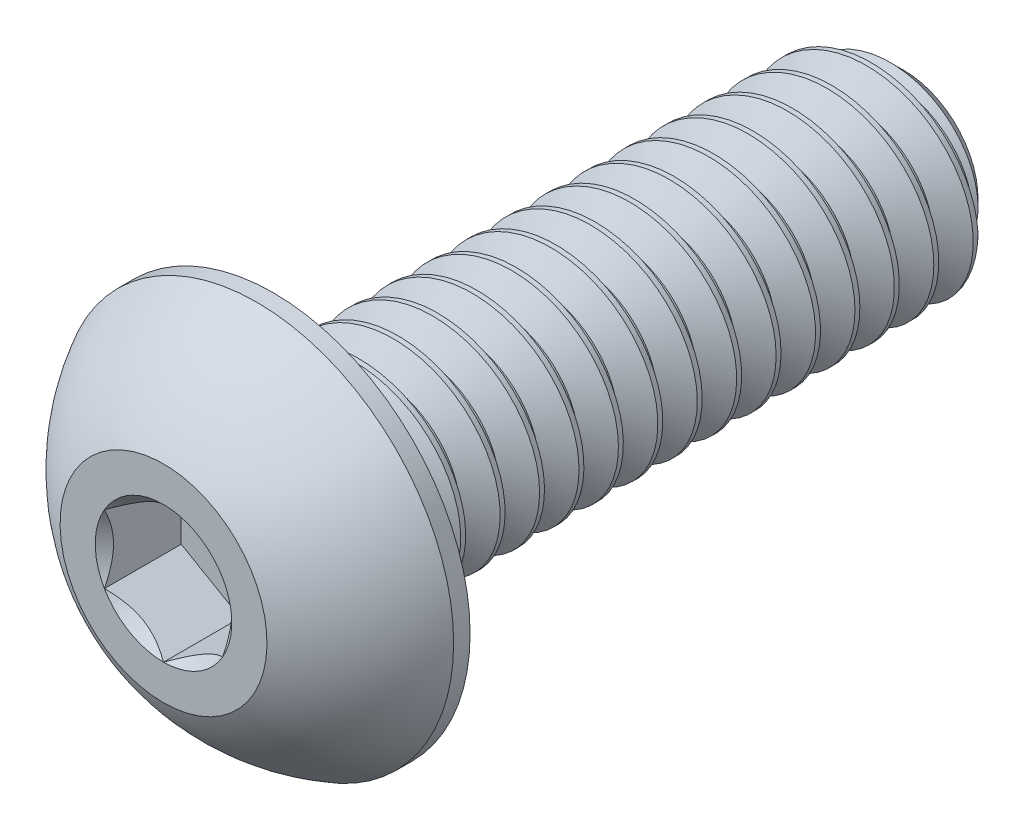
SolidWorks part; units mm, degrees
material "AISI 304"
ref_plane "Front" through (0, 0, 0) normal (0, 0, 1) x (1, 0, 0)
ref_plane "Top" through (0, 0, 0) normal (0, 1, 0) x (1, 0, 0)
ref_plane "Right" through (0, 0, 0) normal (1, 0, 0) x (0, 0, -1)
sketch "Sketch1" plane through (0, 0, 0) normal (1, 0, 0) x (0, 0, -1)
  line L2 (2.2098, 2.0828) -> (14.9098, 2.0828)
  line L3 (14.9098, 2.0828) -> (14.9098, 0)
  line L4 (14.9098, 0) -> (2.2098, 0)
  line L6 (1.8783, 3.9624) -> (2.2098, 3.9624) construction
  line L7 (14.9098, 2.0828) -> (14.9098, -2.0828) construction
  line L8 (0, 0) -> (2.2098, 0) construction
  line L9 (2.2098, 3.9624) -> (2.2098, -3.9624) construction
  line L11 (2.2098, 2.0828) -> (2.2098, 0)
  line L13 (0, 1.1906) -> (0, -1.1906) construction
  line L14 (0, 1.1906) -> (0, 2.0828) construction
  arc A3 (0, 2.0828) -> (1.8783, 3.9624) centre (3.9638, 0) cw construction
  dimension "D1" = 0.3315
  dimension "Head Ht" = 2.2098
  dimension "Head Dia" = 7.9248
  dimension "Dia" = 4.1656
  dimension "Lg" = 12.7
  dimension "Hex" = 2.3813
revolve "Revolve1" add sketch "Sketch1" angle 360 mid plane about L4
sketch "Sketch3" plane through (0, 0, -14.9098) normal (0, 0, -1) x (-1, 0, 0)
  circle A0 centre (0, 0) radius 2.0828
curve "Helix/Spiral1" pitch 0.7937 height 13.4937 turns 17
sketch "Sketch2" plane through (0, 0, 0) normal (1, 0, 0) x (0, 0, -1)
  line L0 (14.9098, 2.0828) -> (15.6043, 2.0828)
  line L1 (15.6043, 2.0828) -> (15.3067, 1.5672)
  line L2 (15.3067, 1.5672) -> (15.2075, 1.5672)
  line L3 (15.2075, 1.5672) -> (14.9098, 2.0828)
  line L4 (15.0586, 1.825) -> (15.4555, 1.825) construction
  dimension "D1" = 60
  dimension "D2" = 0.0992
  dimension "D3" = 0.3969
chamfer "Chamfer1" distance 0.5953 angle 45 1 edges at (0, 2.0828, -14.9098)
sweep "Cut-Sweep1" cut profiles "Sketch2" path "Helix/Spiral1"
sketch "Sketch7" plane through (0, 0, 0) normal (1, 0, 0) x (0, 0, -1)
  line L6 (1.8783, 3.9624) -> (2.2098, 3.9624) construction
  line L8 (0, 0) -> (2.2098, 0) construction
  line L11 (2.2098, 3.9624) -> (2.2098, -3.9624) construction
  line L12 (1.8783, 3.9624) -> (2.2098, 3.9624)
  line L13 (0, 0) -> (2.2098, 0)
  line L14 (0, 1.1906) -> (0, -1.1906) construction
  line L15 (2.2098, 3.9624) -> (2.2098, 0)
  line L16 (0, 2.0828) -> (0, 0)
  arc A2 (1.8783, 3.9624) -> (0, 2.0828) centre (3.9638, 0) ccw construction
  arc A3 (1.8783, 3.9624) -> (0, 2.0828) centre (3.9638, 0) ccw
revolve "Revolve2" add sketch "Sketch7" angle 360 mid plane about L13
sketch "Sketch5" plane through (0, 0, 0) normal (0, 0, 1) x (1, 0, 0)
  line L1 (1.1906, -0.6874) -> (1.1906, 0.6874)
  line L2 (1.1906, 0.6874) -> (0, 1.3748)
  line L3 (0, 1.3748) -> (-1.1906, 0.6874)
  line L4 (-1.1906, 0.6874) -> (-1.1906, -0.6874)
  line L5 (-1.1906, -0.6874) -> (0, -1.3748)
  line L6 (0, -1.3748) -> (1.1906, -0.6874)
  circle A0 centre (0, 0) radius 1.1906 construction
extrude "Cut-Extrude2" cut sketch "Sketch5" against normal blind 1.5469
sketch "Sketch6" plane through (0, 0, 0) normal (0, 0, 1) x (1, 0, 0)
  circle A0 centre (0, 0) radius 1.3748
extrude "Cut-Extrude3" cut sketch "Sketch6" against normal blind 1.5469 draft 45
sketch "Sketch9" [suppressed] plane through (0, 0, -1.4986) normal (0, 0, 1) x (1, 0, 0)
  circle A2 centre (0, 0) radius 1.4224
extrude "Boss-Extrude2" [suppressed] add sketch "Sketch9" against normal offset from surface (12.7 mm away) 31.75
sketch "Sketch10" plane through (0, 0, 0) normal (1, 0, 0) x (0, 0, -1)
  line L0 (14.9098, 2.0828) -> (14.9098, -2.0828) construction
  point P0 (13.7192, -2.0828)
  dimension "D1" = 1.1906
equation "\"D3@Helix/Spiral1\" = \"Lg@Sketch1\" + \"D4@Helix/Spiral1\""
equation "\"D2@Sketch2\" = \"D4@Helix/Spiral1\" * .125"
equation "\"D3@Sketch2\" = \"D4@Helix/Spiral1\" * .5"
equation "\"D1@Chamfer1\" = \"D4@Helix/Spiral1\" * .75"
equation "\"D1@Cut-Extrude2\" = \"Head Ht@Sketch1\" * .7"
equation "\"D1@Sketch1\" = \"Head Ht@Sketch1\" * .15"
equation "\"D1@Sketch10\" = \"D4@Helix/Spiral1\" * 1.5"
equation "\"D1@Cut-Extrude3\" = \"D1@Cut-Extrude2\""
